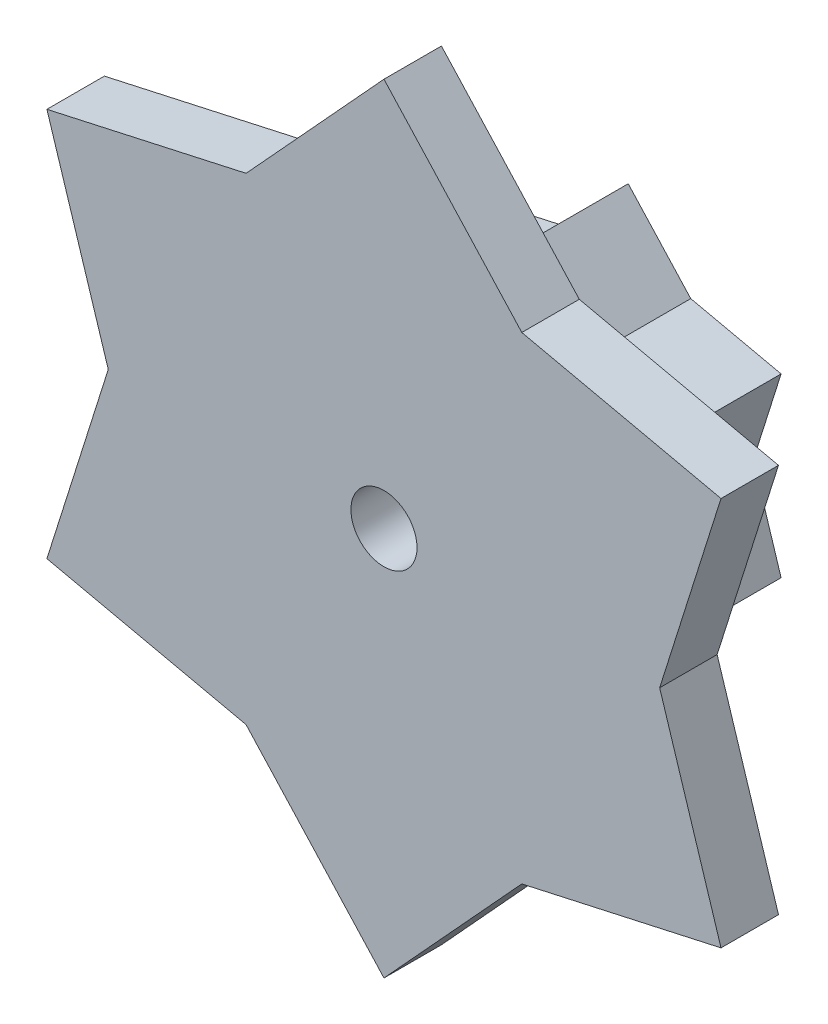
SolidWorks part; units mm, degrees
ref_plane "Front Plane" through (0, 0, 0) normal (0, 0, 1) x (1, 0, 0)
ref_plane "Top Plane" through (0, 0, 0) normal (0, 1, 0) x (1, 0, 0)
ref_plane "Right Plane" through (0, 0, 0) normal (1, 0, 0) x (0, 0, -1)
sketch "Sketch1" plane through (0, 0, 0) normal (0, 0, 1) x (1, 0, 0)
  line L0 (0, 6.1428) -> (0, -5.749) construction
  line L1 (-3.0597, 2.8037) -> (0, 6.1428)
  line L2 (0, 6.1428) -> (3.0597, 2.8037)
  line L3 (0.8982, 4.0516) -> (5.3198, 3.0714)
  line L4 (5.3198, 3.0714) -> (3.9579, -1.2479)
  line L5 (3.9579, 1.2479) -> (5.3198, -3.0714)
  line L6 (5.3198, -3.0714) -> (0.8982, -4.0516)
  line L7 (3.0597, -2.8037) -> (0, -6.1428)
  line L8 (0, -6.1428) -> (-3.0597, -2.8037)
  line L9 (-0.8982, -4.0516) -> (-5.3198, -3.0714)
  line L10 (-5.3198, -3.0714) -> (-3.9579, 1.2479)
  line L11 (-3.9579, -1.2479) -> (-5.3198, 3.0714)
  line L12 (-5.3198, 3.0714) -> (-0.8982, 4.0516)
  circle A0 centre (0, 0) radius 1.15
  circle A1 centre (0, 0) radius 4.15
  point P26 (0, 0)
  dimension "D1" = 2.3
  dimension "D3" = 85
  dimension "D4" = 42.5
  dimension "D2" = 3
  dimension "D5" = 6
extrude "Boss-Extrude1" add sketch "Sketch1" against normal blind 6.5 contours A1 A0 | A1 L1 L12 L11 L10 | L2 L0 A1 L3 | L0 L1 L12 A1 | A1 L12 L1 | A1 L2 L3 | A1 L5 L4 L3 L2 | L0 A1 A0 | A1 L11 L10 L9 L8 | A1 L10 L11 | A1 L8 L9 | A1 L9 L8 L7 L6 | A1 L6 L7 | A1 L7 L6 L5 L4 | A1 L4 L5 | A0 L0 | L0 A0 region at (0.718, 4.7126, 0) region at (-0.718, 4.7126, 0) region at (1.8672, 0, 0) region at (-1.8672, 0, 0) region at (-2.0957, 3.6299, 0) region at (-4.0813, 2.3563, 0) region at (4.0813, 2.3563, 0) region at (2.0957, 3.6299, 0) region at (0.4881, 0, 0) region at (-0.4881, 0, 0) region at (-4.1915, 0, 0) region at (-4.0813, -2.3563, 0) region at (4.1915, 0, 0) region at (4.0813, -2.3563, 0) region at (0.4572, -4.1746, 0) region at (-2.0957, -3.6299, 0) region at (2.0957, -3.6299, 0)
sketch "Sketch2" plane through (0, 0, 0) normal (0, 0, 1) x (1, 0, 0)
  line L0 (4.797, 8.3087) -> (0, 13.5437)
  line L1 (0, 13.5437) -> (-4.797, 8.3087)
  line L2 (-4.797, 8.3087) -> (-11.7292, 6.7719)
  line L3 (-11.7292, 6.7719) -> (-9.594, 0)
  line L4 (-9.594, 0) -> (-11.7292, -6.7719)
  line L5 (-11.7292, -6.7719) -> (-4.797, -8.3087)
  line L6 (-4.797, -8.3087) -> (0, -13.5437)
  line L7 (0, -13.5437) -> (4.797, -8.3087)
  line L8 (4.797, -8.3087) -> (11.7292, -6.7719)
  line L9 (11.7292, -6.7719) -> (9.594, 0)
  line L10 (9.594, 0) -> (11.7292, 6.7719)
  line L11 (11.7292, 6.7719) -> (4.797, 8.3087)
  line L12 (5.3198, -3.0714) -> (4.3514, 0)
  line L13 (4.3514, 0) -> (5.3198, 3.0714)
  line L14 (5.3198, 3.0714) -> (2.1757, 3.7684)
  line L15 (2.1757, 3.7684) -> (0, 6.1428)
  line L16 (0, 6.1428) -> (-2.1757, 3.7684)
  line L17 (-2.1757, 3.7684) -> (-5.3198, 3.0714)
  line L18 (-5.3198, 3.0714) -> (-4.3514, 0)
  line L19 (-4.3514, 0) -> (-5.3198, -3.0714)
  line L20 (-5.3198, -3.0714) -> (-2.1757, -3.7684)
  line L21 (-2.1757, -3.7684) -> (0, -6.1428)
  line L22 (0, -6.1428) -> (2.1757, -3.7684)
  line L23 (2.1757, -3.7684) -> (5.3198, -3.0714)
  line L24 (5.3198, -3.0714) -> (4.3514, 0)
  line L25 (4.3514, 0) -> (5.3198, 3.0714)
  line L26 (5.3198, 3.0714) -> (2.1757, 3.7684)
  line L27 (2.1757, 3.7684) -> (0, 6.1428)
  line L28 (0, 6.1428) -> (-2.1757, 3.7684)
  line L29 (-2.1757, 3.7684) -> (-5.3198, 3.0714)
  line L30 (-5.3198, 3.0714) -> (-4.3514, 0)
  line L31 (-4.3514, 0) -> (-5.3198, -3.0714)
  line L32 (-5.3198, -3.0714) -> (-2.1757, -3.7684)
  line L33 (-2.1757, -3.7684) -> (0, -6.1428)
  line L34 (0, -6.1428) -> (2.1757, -3.7684)
  line L35 (2.1757, -3.7684) -> (5.3198, -3.0714)
  line M25 (5.3198, -3.0714) -> (4.3514, 0)
  line M26 (4.3514, 0) -> (5.3198, 3.0714)
  line M27 (5.3198, 3.0714) -> (2.1757, 3.7684)
  line M28 (2.1757, 3.7684) -> (0, 6.1428)
  line M29 (0, 6.1428) -> (-2.1757, 3.7684)
  line M30 (-2.1757, 3.7684) -> (-5.3198, 3.0714)
  line M31 (-5.3198, 3.0714) -> (-4.3514, 0)
  line M32 (-4.3514, 0) -> (-5.3198, -3.0714)
  line M33 (-5.3198, -3.0714) -> (-2.1757, -3.7684)
  line M34 (-2.1757, -3.7684) -> (0, -6.1428)
  line M35 (0, -6.1428) -> (2.1757, -3.7684)
  line M36 (2.1757, -3.7684) -> (5.3198, -3.0714)
  dimension "D1" = 0
  dimension "D2" = 5
extrude "Boss-Extrude2" add sketch "Sketch2" along normal blind 2 contours M36 M25 M26 M27 M28 M29 M30 M31 M32 M33 M34 M35 | L10 L11 L0 L1 L2 L3 L4 L5 L6 L7 L8 L9 M25 M36 M35 M34 M33 M32 M31 M30 M29 M28 M27 M26 region at (8.1856, 7.1904, 0) region at (0, 0, 0)
extrude "Cut-Extrude1" cut sketch "Sketch1<4>" against normal through all both and the other way through all contours A0 L0 | L0 A0 region at (0.4881, 0, 0) region at (-0.4881, 0, 0)
sketch "Sketch1<4>" plane through (0, 0, 0) normal (0, 0, 1) x (1, 0, 0) same geometry as "Sketch1"
chamfer "Chamfer1" distance 0.4 angle 45 12 edges at (3.7477, -3.4199, 0) (1.0878, -4.9556, 0) (-1.0878, -4.9556, 0) (-3.7477, -3.4199, 0) (-4.8356, -1.5357, 0) (-4.8356, 1.5357, 0) (-3.7477, 3.4199, 0) (4.8356, -1.5357, 0) (4.8356, 1.5357, 0) (3.7477, 3.4199, 0) (1.0878, 4.9556, 0) (-1.0878, 4.9556, 0)
